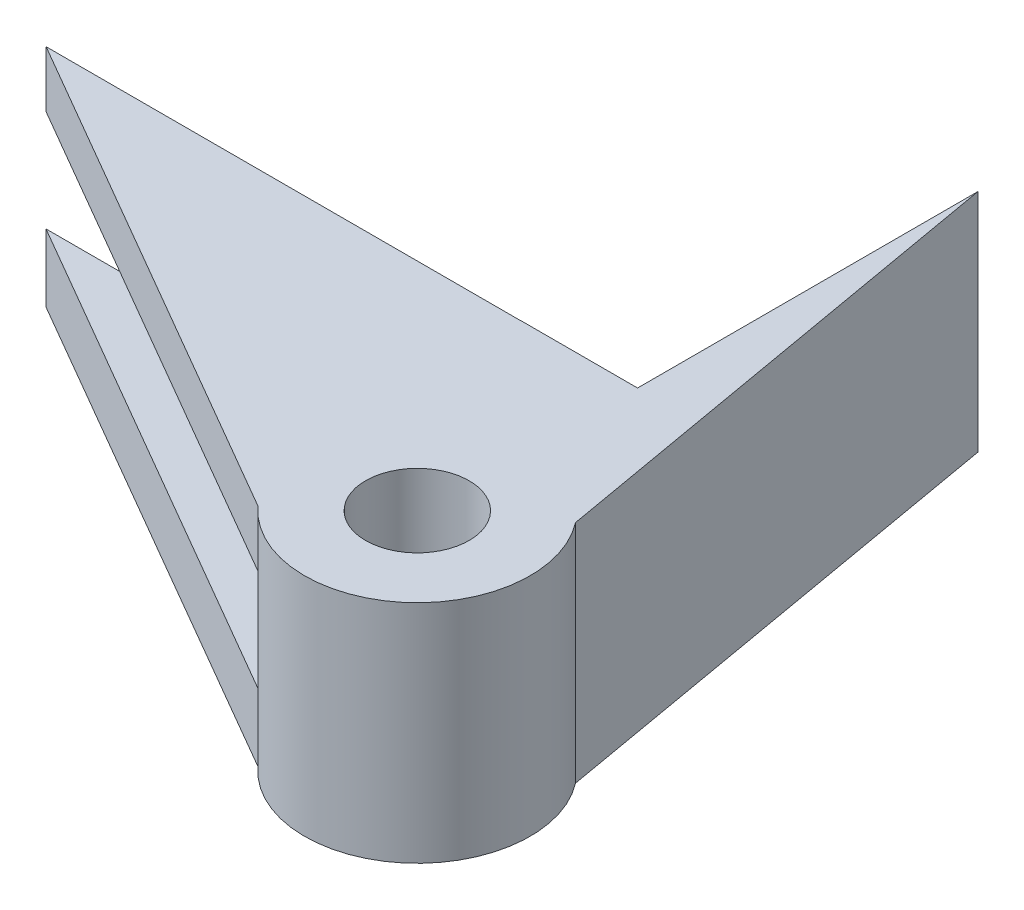
SolidWorks part; units mm, degrees
note: The reader was unsure of these and kept them because the rebuilt part matched: shared geometry of "Sketch1<3>".
ref_plane "Front Plane" through (0, 0, 0) normal (0, 0, 1) x (1, 0, 0)
ref_plane "Top Plane" through (0, 0, 0) normal (0, 1, 0) x (1, 0, 0)
ref_plane "Right Plane" through (0, 0, 0) normal (1, 0, 0) x (0, 0, -1)
sketch "Sketch1" plane through (0, 0, 0) normal (0, 1, 0) x (1, 0, 0)
  line L0 (30.5988, 30.1673) -> (30.5988, 0)
  line L1 (30.5988, 30.1673) -> (38.1766, -13.0728)
  line L2 (0, 0) -> (-21.8247, 0)
  line L3 (-21.8247, 0) -> (22.8292, -25.8724)
  line L4 (30.5988, 0) -> (0, 0)
  line L5 (20.2495, -19.1687) -> (20.2495, 0)
  circle A0 centre (30.2495, -19.1687) radius 10
  circle A1 centre (30.2495, -19.1687) radius 4.5901
  dimension "20" = 20
extrude "Boss-Extrude1" add sketch "Sketch1" along normal blind 6
extrude "Boss-Extrude2" add sketch "Sketch1<3>" along normal blind 20 contours A0 A1 | A0 L1 L0 L4 L5
sketch "Sketch1<3>" plane through (0, 0, 0) normal (0, 1, 0) x (1, 0, 0) same geometry as "Sketch1"
sketch "Sketch2" plane through (0, 20, 0) normal (0, 1, 0) x (1, 0, 0)
  line L0 (37.8034, -12.616) -> (30.1199, 29.7518)
  line L2 (30.1199, 29.7518) -> (30.1199, -0.0126)
  line L3 (30.1199, -0.0126) -> (-21.803, -0.0126)
  line L4 (-21.803, -0.0126) -> (-21.8247, 0)
  line L5 (-21.8247, 0) -> (22.8292, -25.8724) construction
  line L6 (-21.8247, 0) -> (22.8292, -25.8724)
  circle A0 centre (30.2495, -19.1687) radius 10
  circle A1 centre (30.2495, -19.1687) radius 10 construction
  arc A2 (20.2495, -19.1687) -> (38.1766, -13.0728) centre (30.2495, -19.1687) ccw construction
  point P13 (23.7098, -24.9821)
  point P16 (30.5988, 30.7675)
extrude "Boss-Extrude3" add sketch "Sketch2" against normal blind 5
